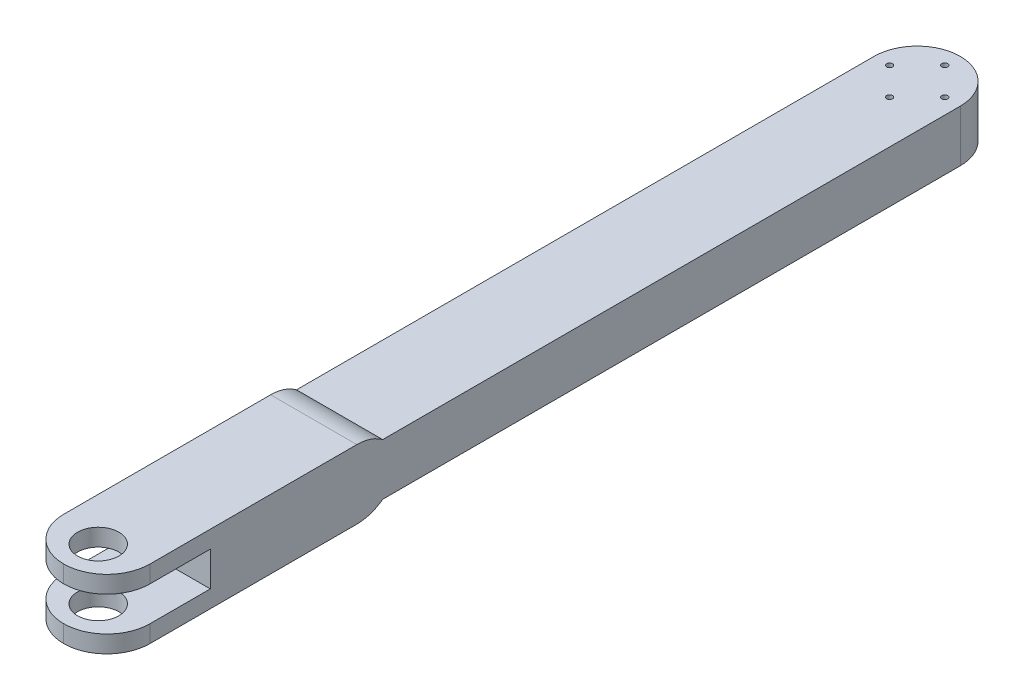
SolidWorks part; units mm, degrees
ref_plane "Plan de face" through (0, 0, 0) normal (0, 0, 1) x (1, 0, 0)
ref_plane "Plan de dessus" through (0, 0, 0) normal (0, 1, 0) x (1, 0, 0)
ref_plane "Plan de droite" through (0, 0, 0) normal (1, 0, 0) x (0, 0, -1)
sketch "Esquisse1" plane through (0, 0, 0) normal (1, 0, 0) x (0, 0, -1)
  line L0 (70, 10) -> (-10, 10)
  line L1 (-10, 10) -> (-10, 5)
  line L2 (70, 10) -> (70, 7.5)
  line L3 (70, 7.5) -> (250, 7.5)
  line L4 (-10, 5) -> (20, 5)
  line L5 (20, 5) -> (20, -5)
  line L6 (250, 7.5) -> (250, -7.5)
  line L7 (11, 0) -> (-11, 0) construction
  line L8 (-10, -5) -> (20, -5)
  line L9 (70, -7.5) -> (250, -7.5)
  line L10 (70, -10) -> (70, -7.5)
  line L11 (-10, -10) -> (-10, -5)
  line L12 (70, -10) -> (-10, -10)
  point P12 (250, 0)
  point P13 (20, 0)
  dimension "10" = 10
  dimension "D2" = 15
  dimension "D3" = 5
  dimension "D4" = 50
  dimension "D5" = 30
  dimension "D6" = 20
  dimension "D7" = 180
extrude "Boss.-Extru.1" add sketch "Esquisse1" along normal mid plane 25
fillet "Congé1" radius 12.5 8 edges at (0, -10, -70) (0, 10, -70) (-12.5, -7.5, 10) (-12.5, 7.5, 10) (12.5, -7.5, 10) (12.5, 7.5, 10) (-12.5, 0, -250) (12.5, 0, -250)
sketch "Esquisse2" plane through (0, 7.5, 0) normal (0, 1, 0) x (1, 0, 0)
  line L0 (-12.5, 237.5) -> (12.5, 237.5) construction
  line L1 (0, 250) -> (0, 226.6844) construction
  arc A0 (0, 250) -> (-12.5, 237.5) centre (0, 237.5) ccw construction
  circle A1 centre (8, 237.5) radius 0.85
  circle A2 centre (0, 245.5) radius 0.85
  circle A3 centre (-8, 237.5) radius 0.85
  circle A4 centre (0, 229.5) radius 0.85
  point P12 (0, 238.3422)
  dimension "D1" = 1.7
  dimension "D2" = 1.7
  dimension "D3" = 8
  dimension "D4" = 8
extrude "Enlèv. mat.-Extru.1" cut sketch "Esquisse2" against normal through all
sketch "Esquisse3" plane through (0, 10, 0) normal (0, 1, 0) x (1, 0, 0)
  circle A0 centre (0, 0) radius 6
  dimension "D1" = 12
extrude "Enlèv. mat.-Extru.2" cut sketch "Esquisse3" against normal through all
